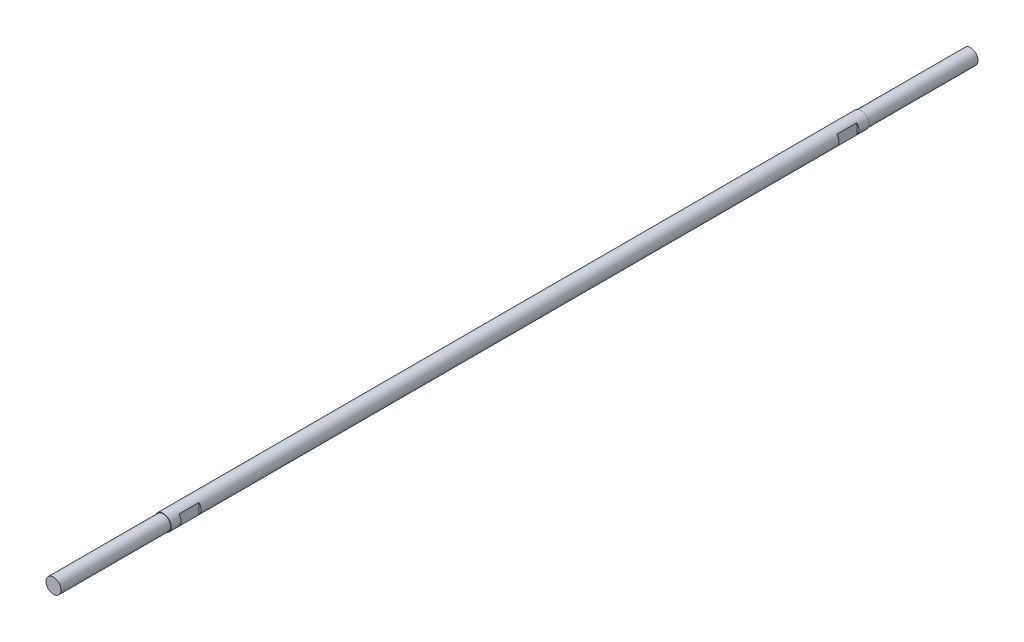
SolidWorks part; units mm, degrees
ref_plane "Front Plane" through (0, 0, 0) normal (0, 0, 1) x (1, 0, 0)
ref_plane "Top Plane" through (0, 0, 0) normal (0, 1, 0) x (1, 0, 0)
ref_plane "Right Plane" through (0, 0, 0) normal (1, 0, 0) x (0, 0, -1)
sketch "Sketch1" plane through (0, 0, 0) normal (0, 0, 1) x (1, 0, 0)
  circle A0 centre (0, 0) radius 4
  dimension "D1" = 8
extrude "Boss-Extrude1" add sketch "Sketch1" along normal blind 460
sketch "Sketch2" plane through (0, 0, 460) normal (0, 0, 1) x (1, 0, 0)
  circle A0 centre (0, 0) radius 3.75
  circle A1 centre (0, 0) radius 4 construction
  circle A2 centre (0, 0) radius 4
  dimension "D1" = 7.5
extrude "Cut-Extrude1" cut sketch "Sketch2" against normal blind 55
extrude "Cut-Extrude2" cut sketch "Sketch2<2>" along normal blind 55 from surface starting at face at (4, 0, 0)
sketch "Sketch2<2>" plane through (0, 0, 460) normal (0, 0, 1) x (1, 0, 0) same geometry as "Sketch2"
sketch "Sketch3" plane through (0, 0, 0) normal (0, 1, 0) x (1, 0, 0)
  line L1 (8, -60) -> (3, -60)
  line L2 (8, -60) -> (8, -70)
  line L3 (8, -70) -> (3, -70)
  line L4 (3, -60) -> (3, -70)
  line L5 (8, -390) -> (3, -390)
  line L6 (8, -390) -> (8, -400)
  line L7 (8, -400) -> (3, -400)
  line L8 (3, -390) -> (3, -400)
  line L9 (0, 0) -> (0, -87.0255) construction
  line L10 (-3.75, -460) -> (3.75, -460) construction
  line L11 (-3.75, -460) -> (3.75, -460)
  point P10 (3, -65)
  point P16 (0, -460)
  point P17 (3, -395)
  dimension "D1" = 10
  dimension "D2" = 5
  dimension "D3" = 65
  dimension "D4" = 3
  dimension "D5" = 65
extrude "Cut-Extrude3" cut sketch "Sketch3" against normal blind 70 and the other way blind 70 contours L5 L8 L7 L6 | L1 L4 L3 L2 region at (5.5, 0, 65) region at (5.5, 0, 395)
